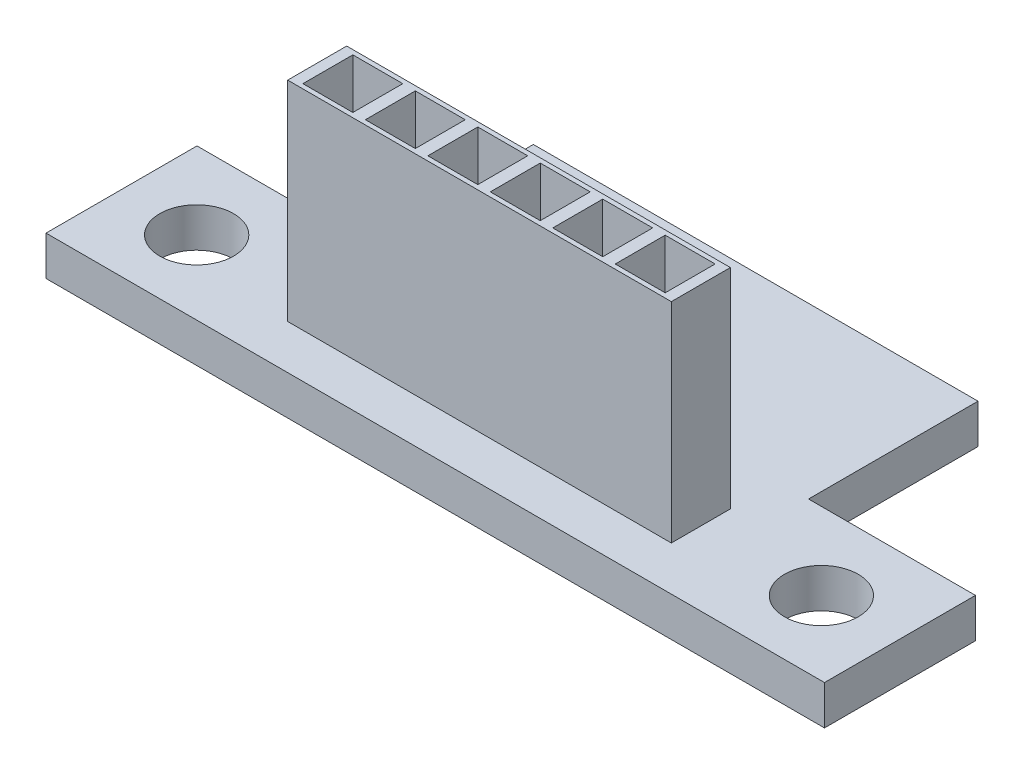
SolidWorks part; units mm, degrees
ref_plane "Front Plane" through (0, 0, 0) normal (0, 0, 1) x (1, 0, 0)
ref_plane "Top Plane" through (0, 0, 0) normal (0, 1, 0) x (1, 0, 0)
ref_plane "Right Plane" through (0, 0, 0) normal (1, 0, 0) x (0, 0, -1)
sketch "Sketch1" plane through (0, 0, 0) normal (0, 1, 0) x (1, 0, 0)
  line L1 (-15.8267, -6.5144) -> (15.8267, -6.5144)
  line L2 (-15.8267, -6.5144) -> (-15.8267, 6.5144)
  line L3 (-15.8267, 6.5144) -> (15.8267, 6.5144)
  line L4 (15.8267, -6.5144) -> (15.8267, 6.5144)
  line L5 (-15.8267, -6.5144) -> (15.8267, 6.5144) construction
  line L6 (-15.8267, 6.5144) -> (15.8267, -6.5144) construction
  point P0 (0, 0)
extrude "Boss-Extrude1" add sketch "Sketch1" along normal blind 1.6
sketch "Sketch2" plane through (0, 1.6, 0) normal (0, 1, 0) x (1, 0, 0)
  line L0 (-12.7, -3.5144) -> (12.7, -3.5144) construction
  line L1 (-7.8, -4.7144) -> (7.8, -4.7144)
  line L2 (-7.8, -4.7144) -> (-7.8, -2.3144)
  line L3 (-7.8, -2.3144) -> (7.8, -2.3144)
  line L4 (7.8, -4.7144) -> (7.8, -2.3144)
  line L5 (-7.8, -4.7144) -> (7.8, -2.3144) construction
  line L6 (-7.8, -2.3144) -> (7.8, -4.7144) construction
  line L7 (-15.8267, -6.5144) -> (15.8267, -6.5144) construction
  circle A0 centre (-12.7, -3.5144) radius 1.5
  circle A1 centre (12.7, -3.5144) radius 1.5
  point P0 (0, -3.5144)
  point P10 (0, -3.5144)
  dimension "D5" = 3
  dimension "D1" = 15.6
  dimension "D2" = 2.4
  dimension "D3" = 25.4
  dimension "D4" = 3
extrude "Boss-Extrude2" add sketch "Sketch2" along normal blind 8.5 separate body contours L1 L4 L3 L2 region at (0, 1.6, 3.5144)
extrude "Cut-Extrude2" cut sketch "Sketch2<3>" against normal through all contours A0 | A1 region at (-12.7, 1.6, 3.5144) region at (12.7, 1.6, 3.5144)
sketch "Sketch2<3>" plane through (0, 1.6, 0) normal (0, 1, 0) x (1, 0, 0) same geometry as "Sketch2"
sketch "Sketch3" plane through (0, 10.1, 0) normal (0, 1, 0) x (1, 0, 0)
  line L0 (-6.35, -3.5144) -> (6.35, -3.5144) construction
  line L5 (7.8, -4.7144) -> (7.8, -2.3144) construction
  line L6 (-2.7949, -4.5296) -> (-2.7949, -2.4993)
  line L7 (-7.3651, -4.5296) -> (-5.3349, -4.5296)
  line L8 (-7.3651, -4.5296) -> (-7.3651, -2.4993)
  line L9 (-7.3651, -2.4993) -> (-5.3349, -2.4993)
  line L10 (-5.3349, -4.5296) -> (-5.3349, -2.4993)
  line L11 (-7.3651, -4.5296) -> (-5.3349, -2.4993) construction
  line L12 (-7.3651, -2.4993) -> (-5.3349, -4.5296) construction
  line L13 (-4.8251, -2.4993) -> (-2.7949, -2.4993)
  line L14 (-4.8251, -4.5296) -> (-4.8251, -2.4993)
  line L15 (-4.8251, -4.5296) -> (-2.7949, -4.5296)
  line L16 (-0.2549, -4.5296) -> (-0.2549, -2.4993)
  line L17 (-2.2851, -2.4993) -> (-0.2549, -2.4993)
  line L18 (-2.2851, -4.5296) -> (-2.2851, -2.4993)
  line L19 (-2.2851, -4.5296) -> (-0.2549, -4.5296)
  line L20 (2.2851, -4.5296) -> (2.2851, -2.4993)
  line L21 (0.2549, -2.4993) -> (2.2851, -2.4993)
  line L22 (0.2549, -4.5296) -> (0.2549, -2.4993)
  line L23 (0.2549, -4.5296) -> (2.2851, -4.5296)
  line L24 (4.8251, -4.5296) -> (4.8251, -2.4993)
  line L25 (2.7949, -2.4993) -> (4.8251, -2.4993)
  line L26 (2.7949, -4.5296) -> (2.7949, -2.4993)
  line L27 (2.7949, -4.5296) -> (4.8251, -4.5296)
  line L28 (7.3651, -4.5296) -> (7.3651, -2.4993)
  line L29 (5.3349, -2.4993) -> (7.3651, -2.4993)
  line L30 (5.3349, -4.5296) -> (5.3349, -2.4993)
  line L31 (5.3349, -4.5296) -> (7.3651, -4.5296)
  point P6 (0, -3.5144)
  point P9 (7.8, -3.5144)
  dimension "D1" = 12.7
  dimension "D3" = 2.54
  dimension "D2" = 6
extrude "Cut-Extrude1" cut sketch "Sketch3" against normal blind 8
sketch "Sketch4" plane through (0, 1.6, 0) normal (0, 1, 0) x (1, 0, 0)
  line L1 (-15.8267, 6.5144) -> (-9.04, 6.5144)
  line L2 (-15.8267, 6.5144) -> (-15.8267, -0.3754)
  line L3 (-15.8267, -0.3754) -> (-9.04, -0.3754)
  line L4 (-9.04, 6.5144) -> (-9.04, -0.3754)
  line L5 (15.8267, 6.5144) -> (9.04, 6.5144)
  line L6 (15.8267, 6.5144) -> (15.8267, -0.3754)
  line L7 (15.8267, -0.3754) -> (9.04, -0.3754)
  line L8 (9.04, 6.5144) -> (9.04, -0.3754)
  point P10 (-8.5083, -3.1432)
  point P11 (-9.04, -0.3754)
extrude "Cut-Extrude3" cut sketch "Sketch4" against normal through all
equation "\"D3@Sketch2\"=1in"
equation "\"D1@Sketch3\"=0.1in*5"
